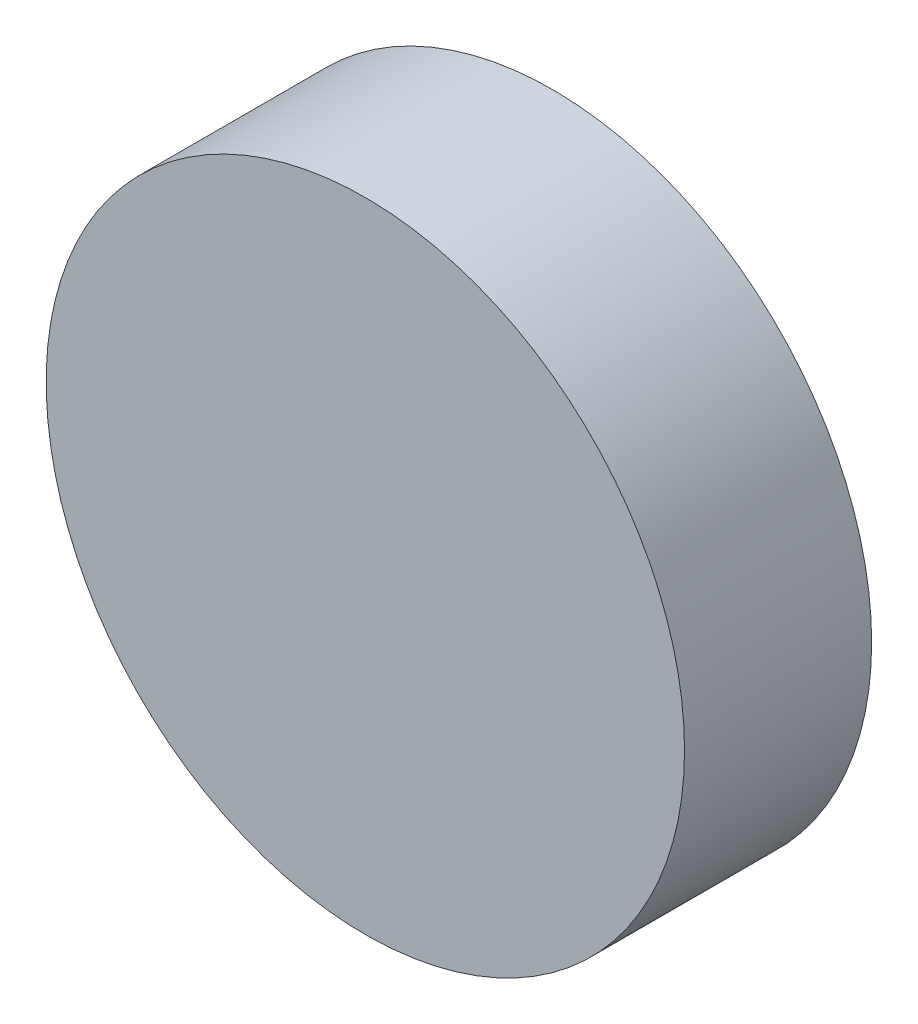
SolidWorks part; units mm, degrees
ref_plane "Front Plane" through (0, 0, 0) normal (0, 0, 1) x (1, 0, 0)
ref_plane "Top Plane" through (0, 0, 0) normal (0, 1, 0) x (1, 0, 0)
ref_plane "Right Plane" through (0, 0, 0) normal (1, 0, 0) x (0, 0, -1)
sketch "Sketch1" plane through (0, 0, 0) normal (0, 0, 1) x (1, 0, 0)
  circle A0 centre (0, 0) radius 36.83
  dimension "D1" = 73.66
extrude "Boss-Extrude2" add sketch "Sketch1" along normal blind 21.59
ref_axis "Axis1" through (0, 0, 26.67) along (0, 0, -1)
